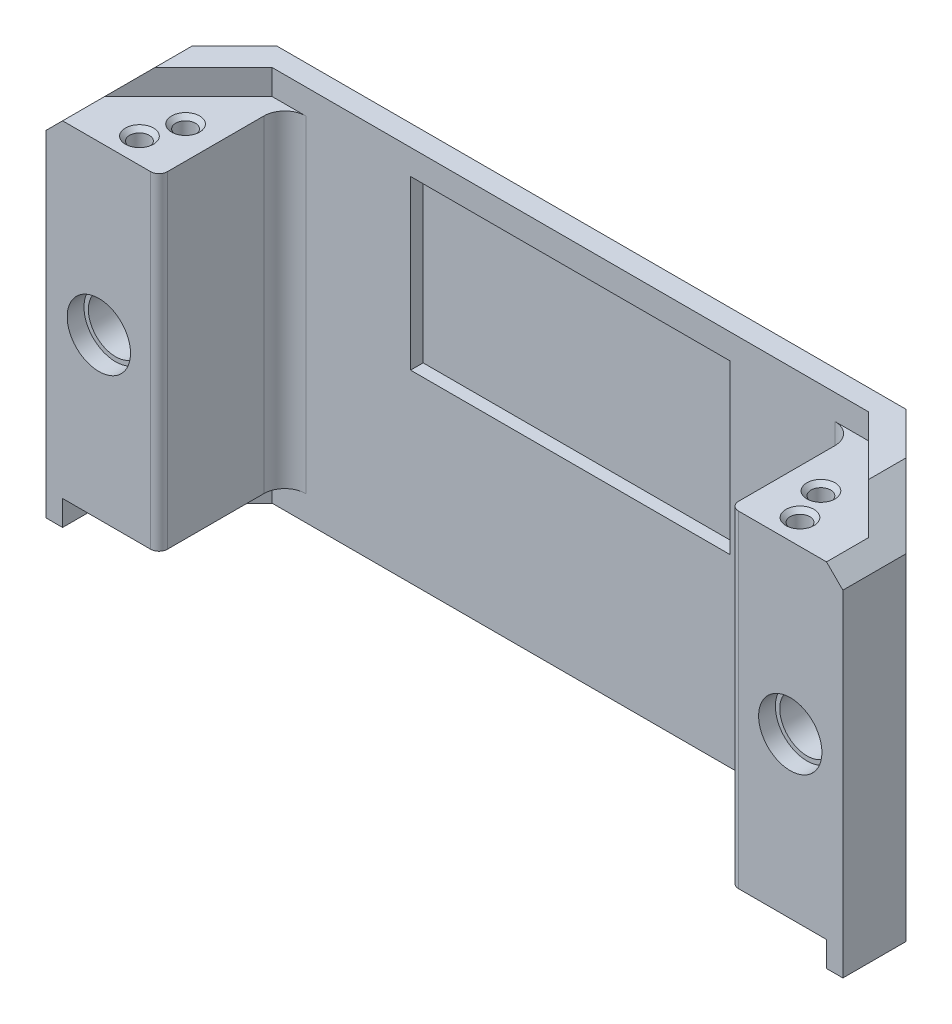
SolidWorks part; units mm, degrees
ref_plane "Front Plane" through (0, 0, 0) normal (0, 0, 1) x (1, 0, 0)
ref_plane "Top Plane" through (0, 0, 0) normal (0, 1, 0) x (1, 0, 0)
ref_plane "Right Plane" through (0, 0, 0) normal (1, 0, 0) x (0, 0, -1)
sketch "Sketch1" plane through (0, 0, 0) normal (0, 0, 1) x (1, 0, 0)
  line L1 (-95, 45) -> (95, 45)
  line L2 (-95, 45) -> (-95, -45)
  line L3 (-95, -45) -> (95, -45)
  line L4 (95, 45) -> (95, -45)
  line L5 (-95, 45) -> (95, -45) construction
  line L6 (-95, -45) -> (95, 45) construction
  point P0 (0, 0)
  point P6 (0, 0)
  dimension "D2" = 190
  dimension "D4" = 90
extrude "Boss-Extrude1" add sketch "Sketch1" along normal blind 5
sketch "Sketch2" plane through (0, 0, 5) normal (0, 0, 1) x (1, 0, 0)
  line L0 (-95, -45) -> (95, -45) construction
  line L1 (-95, 45) -> (-91.1, 45)
  line L2 (-95, 45) -> (-95, -45)
  line L3 (-95, -45) -> (-91.1, -45)
  line L4 (-91.1, 45) -> (-91.1, -45)
  line L5 (0, 0) -> (0, 45) construction
  line L6 (95, 45) -> (-95, 45) construction
  line L7 (95, -45) -> (91.1, -45)
  line L8 (91.1, 45) -> (91.1, -45)
  line L9 (95, 45) -> (91.1, 45)
  line L10 (95, 45) -> (95, -45)
  dimension "D1" = 3.9
extrude "Boss-Extrude2" add sketch "Sketch2" along normal blind 30
sketch "Sketch3" plane through (0, 45, 0) normal (0, 1, 0) x (1, 0, 0)
  line L0 (-91.1, -35) -> (-91.1, -5) construction
  line L1 (-91.1, -14) -> (-57.1, -14)
  line L2 (-91.1, -14) -> (-91.1, -19)
  line L3 (-91.1, -19) -> (-57.1, -19)
  line L4 (-57.1, -14) -> (-57.1, -19)
  line L5 (91.1, -35) -> (91.1, -5) construction
  line L6 (91.1, -14) -> (44.1, -14)
  line L7 (91.1, -14) -> (91.1, -19)
  line L8 (91.1, -19) -> (44.1, -19)
  line L9 (44.1, -14) -> (44.1, -19)
  line L10 (91.1, -5) -> (-91.1, -5) construction
  dimension "D1" = 9
  dimension "D2" = 9
  dimension "D3" = 5
  dimension "D4" = 5
  dimension "D5" = 34
  dimension "D6" = 47
extrude "Boss-Extrude3" add sketch "Sketch3" against normal up to surface (90 mm away) up to face at (0, -45, 18.75)
sketch "Sketch4" plane through (0, 0, 19) normal (0, 0, 1) x (1, 0, 0)
  line L0 (91.1, -45) -> (91.1, 45) construction
  line L1 (-91.1, 45) -> (91.1, 45)
  line L2 (-91.1, 45) -> (-91.1, 39)
  line L3 (-91.1, 39) -> (91.1, 39)
  line L4 (91.1, 45) -> (91.1, 39)
  line L5 (0, 0) -> (-91.1, 0) construction
  line L6 (-91.1, -45) -> (-91.1, 45) construction
  line L7 (-91.1, -39) -> (91.1, -39)
  line L8 (91.1, -45) -> (91.1, -39)
  line L9 (-91.1, -45) -> (91.1, -45)
  line L10 (-91.1, -45) -> (-91.1, -39)
  dimension "D1" = 6
extrude "Cut-Extrude1" cut sketch "Sketch4" against normal blind 5
chamfer "Chamfer6" distance 20 angle 45 4 edges at (91.1, 0, 5) (95, 0, 0) (-95, 0, 0) (-91.1, 0, 5)
sketch "Sketch7" plane through (0, 39, 0) normal (0, 1, 0) x (1, 0, 0)
  line L0 (-85.1, -19) -> (-91.1, -25)
  line L1 (-91.1, -25) -> (-91.1, -35)
  line L2 (-91.1, -35) -> (-68.1, -35)
  line L3 (-68.1, -35) -> (-68.1, -19)
  line L4 (-85.1, -19) -> (-57.1, -19) construction
  line L5 (-68.1, -19) -> (-85.1, -19)
  line L6 (0, 0) -> (0, -5) construction
  line L7 (71.1, -5) -> (-71.1, -5) construction
  line L8 (68.1, -35) -> (68.1, -19)
  line L9 (91.1, -35) -> (68.1, -35)
  line L10 (91.1, -25) -> (91.1, -35)
  line L11 (85.1, -19) -> (91.1, -25)
  line L12 (68.1, -19) -> (85.1, -19)
  dimension "D1" = 23
extrude "Boss-Extrude4" add sketch "Sketch7" against normal up to surface (78 mm away) up to face at (-69.85, -39, 16.5)
fillet "Fillet5" radius 2 2 edges at (-68.1, 0, 35) (68.1, 0, 35)
sketch "Sketch9" plane through (0, 0, 35) normal (0, 0, 1) x (1, 0, 0)
  line L6 (0, 0) -> (0, -45) construction
  line L7 (-71.1, -45) -> (71.1, -45) construction
  line L8 (-95, 45) -> (-95, -45) construction
  line L9 (-95, 39) -> (-82.45, 39) construction
  line L10 (-95, 39) -> (-95, -0.9074) construction
  line L11 (-95, -0.9074) -> (-82.45, -0.9074) construction
  line L12 (-82.45, 39) -> (-82.45, -0.9074) construction
  line L13 (-91.1, 39) -> (-70.1, 39) construction
  circle A0 centre (-82.45, -0.9074) radius 6.5
  circle A1 centre (82.45, -0.9074) radius 6.5
  dimension "D3" = 13
  dimension "D1" = 39.9074
  dimension "D2" = 12.55
extrude "Cut-Extrude4" cut sketch "Sketch9" against normal blind 10
sketch "Sketch10" plane through (0, 0, 35) normal (0, 0, 1) x (1, 0, 0)
  circle A0 centre (-82.45, -0.9074) radius 7.55
  circle A1 centre (82.45, -0.9074) radius 7.55
  dimension "D1" = 15.1
  dimension "D2" = 15.1
extrude "Cut-Extrude5" cut sketch "Sketch10" against normal blind 4
sketch "Sketch15" plane through (0, 39, 0) normal (0, 1, 0) x (1, 0, 0)
  line L0 (68.1, -19) -> (68.1, -33) construction
  line L5 (80.1, -14) -> (44.1, -14) construction
  line L6 (91.1, -35) -> (68.1, -35) construction
  line L7 (91.1, -35) -> (91.1, -14) construction
  line L8 (91.1, -14) -> (68.1, -14) construction
  line L9 (68.1, -35) -> (68.1, -14) construction
  line L10 (68.1, -14) -> (75.7667, -21) construction
  line L11 (75.7667, -21) -> (83.4333, -28) construction
  line L12 (83.4333, -28) -> (91.1, -35) construction
  line L13 (0, 0) -> (0, -5) construction
  line L14 (71.1, -5) -> (-71.1, -5) construction
  line L15 (75.7667, -21) -> (75.7667, -29) construction
  line L16 (75.7667, -29) -> (78.7667, -29) construction
  circle A0 centre (75.7667, -21) radius 2.35
  circle A1 centre (83.4333, -28) radius 2.35 construction
  circle A2 centre (-75.7667, -21) radius 2.35
  circle A3 centre (-83.4333, -28) radius 2.35 construction
  circle A6 centre (78.7667, -29) radius 2.35
  circle A7 centre (-78.7667, -29) radius 2.35
  dimension "D1" = 4.7
  dimension "D2" = 4.7
  dimension "D5" = 4.7
  dimension "D3" = 23
  dimension "D4" = 21
  dimension "D6" = 8
  dimension "D7" = 3
extrude "Cut-Extrude7" cut sketch "Sketch15" against normal blind 8
chamfer "Chamfer7" distance 1 angle 45 4 edges at (-75.7667, 39, 18.65) (75.7667, 39, 23.35) (-78.7667, 39, 26.65) (78.7667, 39, 31.35)
sketch "Sketch17" plane through (0, -39, 0) normal (0, -1, 0) x (1, 0, 0)
  line L0 (0, 0) -> (0, 5) construction
  line L1 (91.1, 35) -> (68.1, 35) construction
  line L2 (91.1, 35) -> (91.1, 19) construction
  line L3 (91.1, 19) -> (68.1, 19) construction
  line L4 (68.1, 35) -> (68.1, 19) construction
  line L5 (-71.1, 5) -> (71.1, 5) construction
  line L6 (68.1, 33) -> (68.1, 19) construction
  line L7 (68.1, 19) -> (44.1, 19) construction
  circle A0 centre (79.6, 27) radius 6.1
  circle A1 centre (-79.6, 27) radius 6.1
  dimension "D2" = 12.2
  dimension "D1" = 11.5
  dimension "D3" = 8
  dimension "D4" = 11.5
extrude "Cut-Extrude8" cut sketch "Sketch17" against normal blind 3.2
fillet "Fillet7" radius 0.2 2 edges at (-85.7, -39, 27) (85.7, -39, 27)
chamfer "Chamfer8" distance 9.9 angle 45 2 edges at (-95, 45, 27.5) (95, 45, 27.5)
sketch "Sketch18" plane through (-57.1, 0, 0) normal (1, 0, 0) x (0, 0, -1)
  line L1 (-19, 39) -> (-14, 39)
  line L2 (-19, 39) -> (-19, -39)
  line L3 (-19, -39) -> (-14, -39)
  line L4 (-14, 39) -> (-14, -39)
extrude "Cut-Extrude9" cut sketch "Sketch18" against normal up to surface and the other way up to surface up to face at (-68.1, 0, 26) other way up to face at (68.1, 0, 26)
sketch "Sketch20" plane through (0, 39, 0) normal (0, 1, 0) x (1, 0, 0)
  line L0 (-68.1, -14) -> (-68.1, -5)
  line L1 (71.1, -5) -> (-71.1, -5) construction
  line L2 (-68.1, -5) -> (-71.1, -5)
  line L3 (-71.1, -5) -> (-80.1, -14)
  line L4 (-80.1, -14) -> (-68.1, -14)
  line L5 (0, 0) -> (0, -5) construction
  line L6 (71.1, -5) -> (80.1, -14)
  line L7 (68.1, -5) -> (71.1, -5)
  line L8 (68.1, -14) -> (68.1, -5)
  line L9 (80.1, -14) -> (68.1, -14)
extrude "Boss-Extrude5" add sketch "Sketch20" against normal up to surface (78 mm away) up to face at (-85.9, -39, 27)
fillet "Fillet8" radius 5 2 edges at (68.1, 0, 5) (-68.1, 0, 5)
sketch "Sketch21" plane through (0, 0, 5) normal (0, 0, 1) x (1, 0, 0)
  line L1 (-38.1, 39) -> (38.1, 39)
  line L2 (-38.1, 39) -> (-38.1, -1)
  line L3 (-38.1, -1) -> (38.1, -1)
  line L4 (38.1, 39) -> (38.1, -1)
  line L5 (71.1, 45) -> (-71.1, 45) construction
  line L6 (-63.1, 39) -> (-63.1, -39) construction
  line L7 (63.1, -39) -> (63.1, 39) construction
  dimension "D1" = 6
  dimension "D2" = 40
  dimension "D3" = 25
  dimension "D4" = 25
extrude "Cut-Extrude10" cut sketch "Sketch21" against normal blind 3
